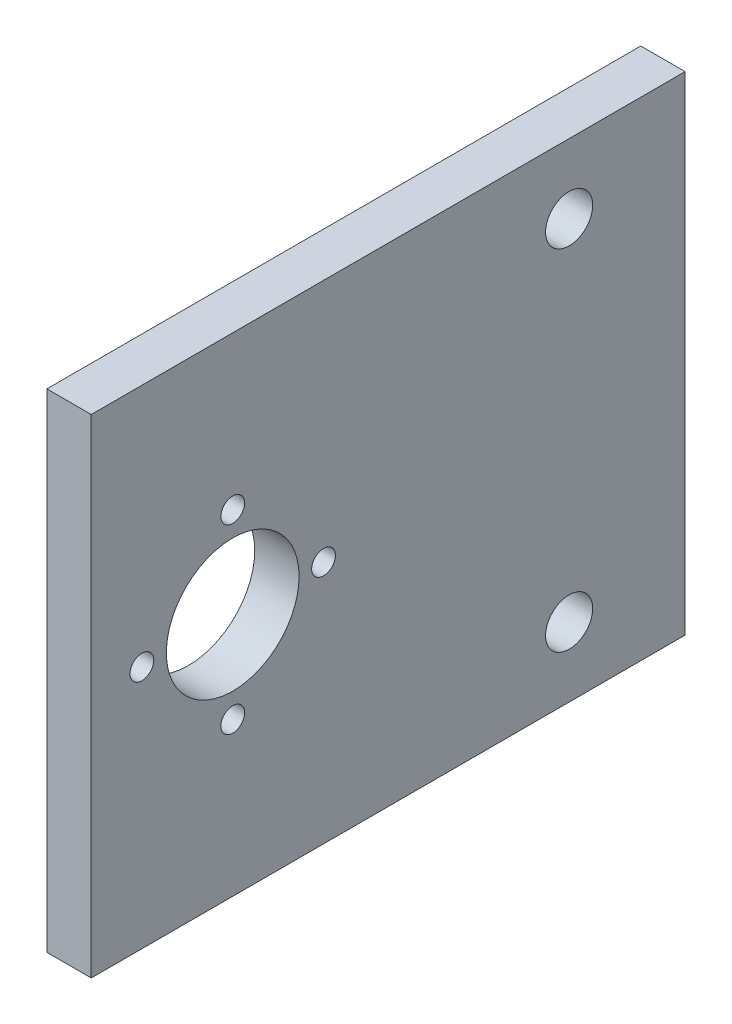
SolidWorks part; units mm, degrees
ref_plane "Front Plane" through (0, 0, 0) normal (1, 0, 0) x (0, 1, 0)
ref_plane "Top Plane" through (0, 0, 0) normal (0, 0, 1) x (0, 1, 0)
ref_plane "Right Plane" through (0, 0, 0) normal (0, 1, 0) x (-1, 0, 0)
sketch "Sketch1" plane through (0, 0, 0) normal (1, 0, 0) x (0, 1, 0)
  line L0 (0, 42.5) -> (0, -42.5) construction
  line L1 (-34.925, -42.5) -> (34.925, -42.5)
  line L2 (-34.925, -42.5) -> (-34.925, 42.5)
  line L3 (-34.925, 42.5) -> (34.925, 42.5)
  line L4 (34.925, -42.5) -> (34.925, 42.5)
  line L5 (-34.925, -42.5) -> (34.925, 42.5) construction
  line L6 (-34.925, 42.5) -> (34.925, -42.5) construction
  line L7 (-34.925, 22.25) -> (34.925, 22.25) construction
  line L9 (-25, -25.9) -> (25, -25.9) construction
  line L10 (-25, -25.9) -> (-25, 25.9) construction
  line L11 (-25, 25.9) -> (25, 25.9) construction
  line L12 (25, -25.9) -> (25, 25.9) construction
  line L13 (-25, -25.9) -> (25, 25.9) construction
  line L14 (-25, 25.9) -> (25, -25.9) construction
  circle A1 centre (0, 35.25) radius 1.7
  circle A2 centre (0, 9.25) radius 1.7
  circle A3 centre (-13, 22.25) radius 1.7
  circle A4 centre (13, 22.25) radius 1.7
  circle A5 centre (0, 22.25) radius 9.5
  circle A6 centre (-25, -25.9) radius 3.3731
  circle A7 centre (25, -25.9) radius 3.3731
  point P0 (0, 0)
  point P20 (0, 0)
  dimension "D5" = 3.4
  dimension "D7" = 13
  dimension "D8" = 19
  dimension "D12" = 6.7462
  dimension "D1" = 69.85
  dimension "D2" = 85
  dimension "D3" = 64.75
  dimension "D4" = 13
  dimension "D9" = 16.6
  dimension "D10" = 50
extrude "Boss-Extrude1" add sketch "Sketch1" along normal blind 6.35
